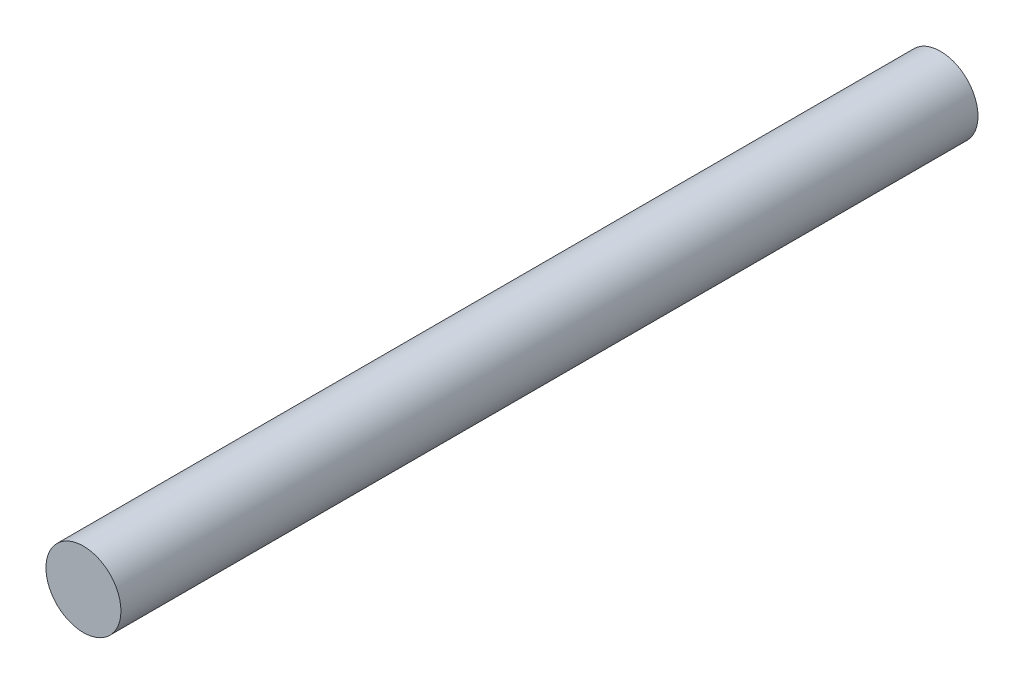
SolidWorks part; units mm, degrees
material "Stainless Steel (ferritic)"
ref_plane "Vorne" through (0, 0, 0) normal (0, 0, 1) x (1, 0, 0)
ref_plane "Oben" through (0, 0, 0) normal (0, 1, 0) x (1, 0, 0)
ref_plane "Rechts" through (0, 0, 0) normal (1, 0, 0) x (0, 0, -1)
ref_axis "Achse1" through (-80.9, 0, 0) along (1, 0, 0)
ref_axis "Achse2" through (0, 0, -80.9) along (0, 0, 1)
sketch "Skizze1" plane through (0, 0, 0) normal (0, 0, 1) x (1, 0, 0)
  circle A0 centre (0, 0) radius 0.525
  dimension "D1" = 1.05
extrude "Aufsatz-Linear austragen1" add sketch "Skizze1" along normal blind 12
